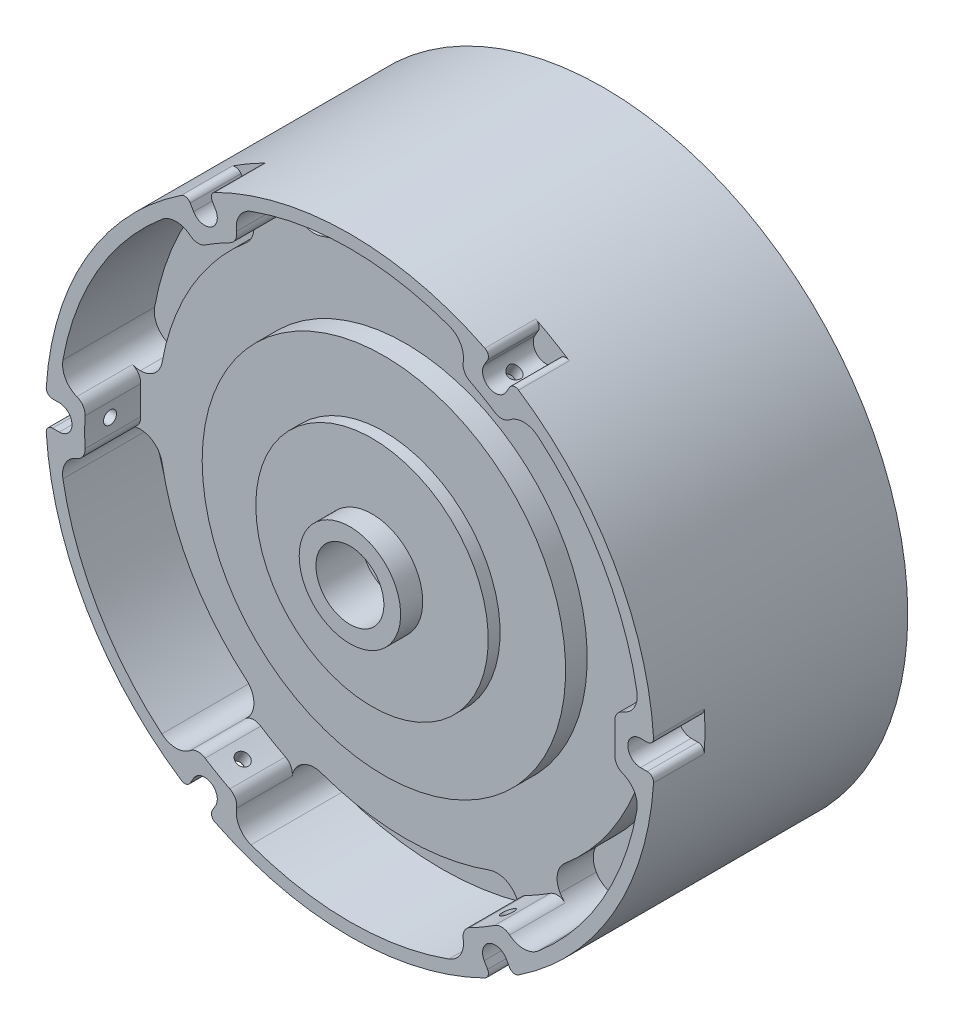
SolidWorks part; units mm, degrees
material "6061-T6 (SS)"
ref_plane "Front Plane" through (0, 0, 0) normal (0, 0, 1) x (1, 0, 0)
ref_plane "Top Plane" through (0, 0, 0) normal (0, 1, 0) x (1, 0, 0)
ref_plane "Right Plane" through (0, 0, 0) normal (1, 0, 0) x (0, 0, -1)
sketch "Sketch2" plane through (0, 0, 0) normal (0, 1, 0) x (1, 0, 0)
  line L0 (0, 11.176) -> (0, 0)
  line L2 (-76.2, 0) -> (-76.2, 46.101)
  line L3 (-76.2, 46.101) -> (-69.85, 46.101) construction
  line L4 (-69.85, 46.101) -> (-34.925, 46.101) construction
  line L5 (-34.925, 46.101) -> (0, 46.101) construction
  line L6 (-76.2, 0) -> (-73.025, 0)
  line L13 (-73.025, 0) -> (-73.025, 22.9805)
  line L14 (-73.025, 22.9805) -> (-61.9125, 22.9805)
  line L15 (-61.9125, 22.9805) -> (-61.9125, 13.9169)
  line L16 (-61.9125, 13.9169) -> (-45.5083, 13.9169)
  line L17 (-45.5083, 13.9169) -> (-45.5083, 8.5103)
  line L18 (-45.5083, 8.5103) -> (-29.1042, 8.5103)
  line L19 (-29.1042, 8.5103) -> (-29.1042, 5.5363)
  line L20 (0, 46.101) -> (0, 11.176) construction
  line L21 (-45.5083, 13.9169) -> (0, 46.101) construction
  line L22 (-61.9125, 22.9805) -> (0, 46.101) construction
  line L23 (0, 46.101) -> (-29.1042, 8.5103) construction
  line L24 (-29.1042, 5.5363) -> (-12.7, 5.5363)
  line L25 (-12.7, 5.5363) -> (-12.7, 0)
  line L26 (-12.7, 0) -> (0, 0)
  line L27 (0, 46.101) -> (-12.7, 5.5363) construction
  line L28 (-69.85, 46.101) -> (-69.85, 63.5)
  line L29 (-69.85, 63.5) -> (-76.2, 63.5)
  line L30 (-76.2, 63.5) -> (-76.2, 46.101)
  ellipse E0 centre (0, 46.101) end of major axis (69.85, 46.101) minor radius 34.925 construction
  ellipse E1 centre (0, 46.101) end of major axis (69.85, 46.101) minor radius 34.925 (-69.85, 46.101) -> (0, 11.176) ccw
  point P2 (-10.8028, 11.5962)
  point P7 (-55.9638, 25.202)
  point P16 (-25.2167, 13.5313)
  point P18 (-40.3238, 17.5834)
  dimension "D3" = 11.176
  dimension "D6" = 6.35
  dimension "D7" = 6.35
  dimension "D11" = 63.5
  dimension "D2" = 76.2
  dimension "D4" = 11.1125
  dimension "D5" = 3.175
  dimension "D8" = 6.35
  dimension "D9" = 6.35
  dimension "D10" = 12.7
  dimension "D12" = 6.35
  dimension "D13" = 52.324
  dimension "D14" = 17.399
revolve "Revolve1" add sketch "Sketch2" angle 360 about L20
sketch "Sketch5" plane through (0, 0, 0) normal (0, 0, 1) x (1, 0, 0)
  circle A0 centre (0, 0) radius 8.509
  dimension "D1" = 17.018
extrude "Cut-Extrude2" cut sketch "Sketch5" against normal through all
sketch "Sketch11" plane through (0, 0, 0) normal (0, 0, 1) x (1, 0, 0)
  line L0 (-76.1338, 3.175) -> (-72.771, 3.175)
  line L1 (-76.1338, -3.175) -> (-72.771, -3.175)
  line L2 (-75.935, 6.35) -> (-61.586, 6.35)
  line L3 (-61.586, 6.35) -> (-61.586, -6.35)
  line L4 (-61.586, -6.35) -> (-75.935, -6.35)
  circle A0 centre (0, 0) radius 76.2 construction
  arc A1 (-72.771, -3.175) -> (-72.771, 3.175) centre (-72.771, 0) ccw
  arc A2 (-76.1338, 3.175) -> (-76.1338, -3.175) centre (0, 0) ccw
  circle A3 centre (0, 0) radius 61.9125 construction
  circle A4 centre (0, 0) radius 61.9125 construction
  arc A5 (-76.1338, -3.175) -> (-75.935, -6.35) centre (-76.3902, -4.7848) cw
  arc A6 (-75.935, 6.35) -> (-76.1338, 3.175) centre (-76.5368, 4.794) cw
  point P8 (-69.596, 0)
  point P20 (-76.2, 0)
  circle M6 centre (0, 0) radius 73.025
  circle M7 centre (0, 0) radius 76.2
  dimension "D1" = 6.35
  dimension "D2" = 3.175
  dimension "D3" = 6.604
extrude "Boss-Extrude2" add sketch "Sketch11" against normal up to surface (22.9805 mm away) contours A1 L4 L3 L2 M6 | A1 M6 | A1 L0 L1 M6 M7 region at (-74.59, 0, 0) region at (-66.6747, 0, 0) region at (-71.5476, 0, 0) up to face at (-61.9125, 0, -22.9805)
sketch "Sketch12" plane through (0, 0, 0) normal (0, 0, 1) x (1, 0, 0)
  line L0 (-76.1338, 3.175) -> (-72.771, 3.175)
  line L1 (-76.1338, -3.175) -> (-72.771, -3.175)
  arc A1 (-72.771, 3.175) -> (-72.771, -3.175) centre (-72.771, 0) cw
  arc A3 (-76.1338, -3.175) -> (-76.1338, 3.175) centre (-76.1338, 0) cw
  point P10 (-69.596, 0)
extrude "Cut-Extrude4" cut sketch "Sketch12" against normal blind 12.7
hole_wizard "#30 (0.1285) Diameter Hole1" positions "Sketch13" profile "Sketch14" hole size "#30" standard "ANSI Inch" end condition through all
sketch "Sketch13" plane through (-61.586, 0, 0) normal (1, 0, 0) x (0, 0, -1)
  line L0 (0, 6.35) -> (0, -6.35) construction
  point P0 (6.35, 0)
  dimension "D1" = 6.35
sketch "Sketch14" plane through (-61.586, 0, -6.35) normal (0, 1, 0) x (0, 0, -1)
  line L0 (0, 0) -> (0, 14.614)
  line L1 (0, 14.614) -> (1.6319, 14.614)
  line L2 (1.6319, 14.614) -> (1.6319, 0)
  line L5 (1.6319, 0) -> (0, 0)
  line L11 (0, -6.35) -> (0, 107.95) construction
  dimension "Thru Hole Dia." = 3.2639
  dimension "Thru Hole Depth" = 14.614
fillet "Fillet3" radius 5.5562 4 edges at (-72.7484, -6.35, -11.4902) (-72.7484, 6.35, -11.4902) (-61.586, -6.35, -18.4487) (-61.586, 6.35, -18.4487)
fillet "Fillet5" radius 1.5875 2 edges at (-76.1338, -3.175, -6.35) (-76.1338, 3.175, -6.35)
pattern_circular "CirPattern3" count 6 over 360 about axis through (0, 0, 0) along (0, 0, -1) of "Boss-Extrude2", "Cut-Extrude4", "#30 (0.1285) Diameter Hole1", "Fillet3", "Fillet5"
sketch "Sketch15" plane through (0, 0, 0) normal (0, 0, 1) x (1, 0, 0)
  line L0 (-61.586, 6.35) -> (-61.586, -6.35) construction
  circle A0 centre (0, 0) radius 61.586
  circle A1 centre (0, 0) radius 66.421
  point P4 (-66.421, 0)
  dimension "D1" = 3.175
extrude "Cut-Extrude6" cut sketch "Sketch15" against normal up to surface (13.9169 mm away) up to face at (-45.5083, 0, -13.9169)
fillet "Fillet6" radius 3.175 12 edges at (-66.1168, 6.35, -6.9584) (-66.1168, -6.35, -6.9584) (38.5576, 54.0838, -6.9584) (-38.5576, 54.0838, -6.9584) (-27.5591, 60.4338, -6.9584) (27.5591, 60.4338, -6.9584) (66.1168, -6.35, -6.9584) (66.1168, 6.35, -6.9584) (38.5576, -54.0838, -6.9584) (27.5591, -60.4338, -6.9584) (-27.5591, -60.4338, -6.9584) (-38.5576, -54.0838, -6.9584)
equation "\"beams\"= 6"
equation "\"D1@CirPattern3\"=\"beams\""
